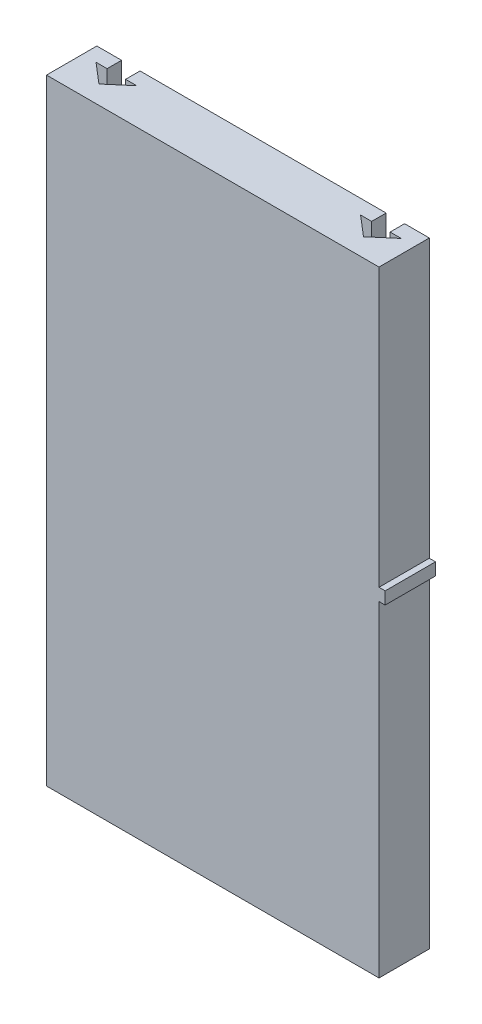
SolidWorks part; units mm, degrees
ref_plane "Alzado" through (0, 0, 0) normal (0, 0, 1) x (1, 0, 0)
ref_plane "Planta" through (0, 0, 0) normal (0, 1, 0) x (1, 0, 0)
ref_plane "Vista lateral" through (0, 0, 0) normal (1, 0, 0) x (0, 0, -1)
sketch "Croquis1" plane through (0, 0, 0) normal (0, 1, 0) x (1, 0, 0)
  line L1 (-27, 2.1573) -> (-27, 10.3309)
  line L2 (-27, 10.3309) -> (-22.9823, 10.3309)
  line L7 (27, 10.3309) -> (27, 2.1573)
  line L8 (0, -1.1135) -> (0, 19.1205) construction
  line L9 (-24.7823, 7.9809) -> (-22.9823, 7.9809)
  line L11 (-19.9823, 10.3309) -> (-19.9823, 7.9809)
  line L13 (-22.9823, 10.3309) -> (-22.9823, 7.9809)
  line L15 (27, 10.3309) -> (22.9823, 10.3309)
  line L16 (-19.9823, 7.9809) -> (-18.1823, 7.9809)
  line L17 (-24.7823, 7.9809) -> (-21.4823, 5.1573)
  line L18 (-21.4823, 5.1573) -> (-18.1823, 7.9809)
  line L26 (-19.9823, 10.3309) -> (-19, 10.3309)
  line L27 (-21.4823, 5.1573) -> (-21.4823, 10.784) construction
  line L29 (-27, 2.1573) -> (27, 2.1573)
  line L30 (-19.9823, 7.9809) -> (-18.1823, 7.9809)
  line L31 (-19.9823, 7.9809) -> (-18.1823, 7.9809)
  line L32 (19.9823, 10.3309) -> (19.9823, 7.9809)
  line L33 (19.9823, 7.9809) -> (18.1823, 7.9809)
  line L34 (21.4823, 5.1573) -> (18.1823, 7.9809)
  line L35 (24.7823, 7.9809) -> (21.4823, 5.1573)
  line L36 (24.7823, 7.9809) -> (22.9823, 7.9809)
  line L37 (22.9823, 10.3309) -> (22.9823, 7.9809)
  line L38 (19.9823, 10.3309) -> (-19, 10.3309)
  point P11 (-21, 12.065)
  dimension "D3" = 1.5
  dimension "D4" = 1.8
  dimension "D5" = 1.5
  dimension "D6" = 1.8
  dimension "D7" = 27
  dimension "D8" = 27
  dimension "D11" = 3
extrude "Saliente-Extruir1" add sketch "Croquis1" along normal blind 100 contours L38 L26 L11 L16 L18 L17 L9 L13 L2 L1 L29 L7 L15 L33 region at (0, 0, -6.1073)
sketch "Sketch1" plane through (0, 0, -10.3309) normal (0, 0, -1) x (-1, 0, 0)
  circle A0 centre (0, 68.0835) radius 19
  dimension "D1" = 38
extrude "Cut-Extrude1" cut sketch "Sketch1" against normal blind 3.4
sketch "Sketch2" plane through (0, 0, -10.3309) normal (0, 0, -1) x (-1, 0, 0)
  line L1 (1.2674, 86.8546) -> (28.1957, 86.8546)
  line L8 (28.1957, 48.7525) -> (28.1957, 86.8546)
  line L9 (-0.7613, 48.7525) -> (-2.0438, 50.8128)
  line L10 (-2.0438, 50.8128) -> (-2.0438, 86.9733)
  line L11 (-2.0438, 86.9733) -> (1.2674, 86.8546)
  line L12 (-0.7613, 48.7525) -> (28.1957, 48.7525)
  circle A0 centre (0, 68.0835) radius 19 construction
  point P0 (0, 68.0835)
sketch "Sketch3" plane through (-27, 0, 0) normal (-1, 0, 0) x (0, 0, 1)
  line L1 (-3.1841, 70.4673) -> (-9.6237, 70.4673)
  line L2 (-3.1841, 70.4673) -> (-3.1841, 50.5292)
  line L3 (-3.1841, 50.5292) -> (-9.6237, 50.5292)
  line L4 (-9.6237, 70.4673) -> (-9.6237, 50.5292)
  line L5 (-3.1841, 70.4673) -> (-9.6237, 50.5292) construction
  line L6 (-3.1841, 50.5292) -> (-9.6237, 70.4673) construction
  point P0 (-6.4039, 60.4982)
extrude "Cut-Extrude3" cut sketch "Sketch3" against normal blind 12
extrude "Cut-Extrude4" cut sketch "Sketch2" against normal blind 3.3 contours L8 L1 region at (-13.0904, 67.8279, -10.3309)
sketch "Sketch4" plane through (27, 0, 0) normal (1, 0, 0) x (0, 0, -1)
  line L0 (2.1573, 100) -> (2.1573, 0) construction
  line L1 (2.1573, 54.9534) -> (10.3309, 54.9534)
  line L2 (2.1573, 54.9534) -> (2.1573, 52.9534)
  line L3 (2.1573, 52.9534) -> (10.3309, 52.9534)
  line L4 (10.3309, 54.9534) -> (10.3309, 52.9534)
  line L5 (10.3309, 100) -> (10.3309, 0) construction
  dimension "D1" = 2
extrude "Boss-Extrude1" add sketch "Sketch4" along normal blind 1
